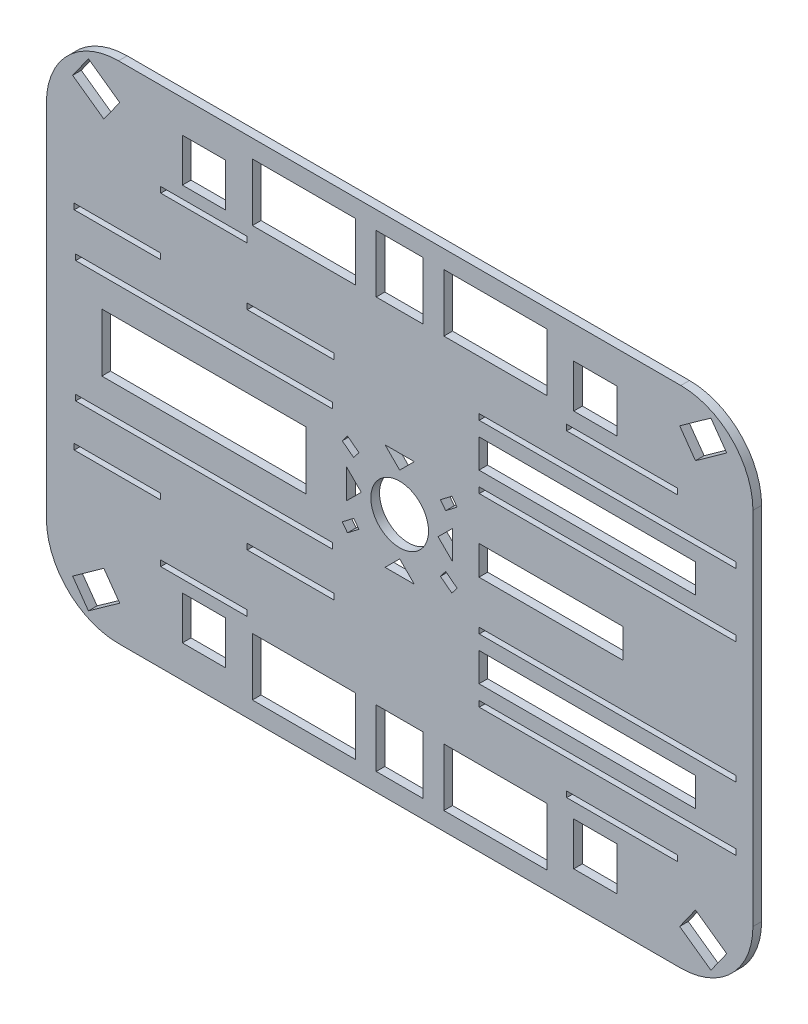
SolidWorks part; units mm, degrees
material "Hexcel AS4C (3000 Filaments)"
ref_plane "Front Plane" through (0, 0, 0) normal (0, 0, 1) x (1, 0, 0)
ref_plane "Top Plane" through (0, 0, 0) normal (0, 1, 0) x (1, 0, 0)
ref_plane "Right Plane" through (0, 0, 0) normal (1, 0, 0) x (0, 0, -1)
sketch "Sketch1" plane through (0, 0, 0) normal (0, 0, 1) x (1, 0, 0)
  line L1 (-122.5, 87.5) -> (122.5, 87.5)
  line L2 (-122.5, 87.5) -> (-122.5, -87.5)
  line L3 (-122.5, -87.5) -> (122.5, -87.5)
  line L4 (122.5, 87.5) -> (122.5, -87.5)
  line L5 (-122.5, 87.5) -> (122.5, -87.5) construction
  line L6 (-122.5, -87.5) -> (122.5, 87.5) construction
  point P0 (0, 0)
  dimension "D1" = 245
  dimension "D2" = 175
extrude "Boss-Extrude1" add sketch "Sketch1" along normal blind 3
sketch "Sketch2" plane through (0, 0, 3) normal (0, 0, 1) x (1, 0, 0)
  line L0 (0, 0) -> (-160.2379, 0) construction
  line L1 (0, 0) -> (163.7011, 0) construction
  line L2 (0, 94.1714) -> (0, -99.7658) construction
  line L3 (-52.8572, 37.0745) -> (-22.8572, 37.0745)
  line L4 (-103.2826, 10.0745) -> (-32.4317, 10.0745)
  line L5 (-103.2826, 10.0745) -> (-103.2826, -10.0745)
  line L6 (-103.2826, -10.0745) -> (-32.4317, -10.0745)
  line L7 (-32.4317, 10.0745) -> (-32.4317, -10.0745)
  line L8 (-103.2826, 10.0745) -> (-32.4317, -10.0745) construction
  line L9 (-103.2826, -10.0745) -> (-32.4317, 10.0745) construction
  line L10 (-112.3571, 22.0745) -> (-23.3572, 22.0745)
  line L11 (-112.3571, 22.0745) -> (-112.3571, 20.0745)
  line L12 (-112.3571, 20.0745) -> (-23.3572, 20.0745)
  line L13 (-23.3572, 22.0745) -> (-23.3572, 20.0745)
  line L14 (-112.3571, 22.0745) -> (-23.3572, 20.0745) construction
  line L15 (-112.3571, 20.0745) -> (-23.3572, 22.0745) construction
  line L16 (-52.8572, 37.0745) -> (-52.8572, 35.0745)
  line L17 (-52.8572, 35.0745) -> (-22.8572, 35.0745)
  line L18 (-22.8572, 37.0745) -> (-22.8572, 35.0745)
  line L19 (-52.8572, 37.0745) -> (-22.8572, 35.0745) construction
  line L20 (-52.8572, 35.0745) -> (-22.8572, 37.0745) construction
  line L21 (-112.8572, 37.0745) -> (-82.8572, 37.0745)
  line L22 (-112.8572, 37.0745) -> (-112.8572, 35.0745)
  line L23 (-112.8572, 35.0745) -> (-82.8572, 35.0745)
  line L24 (-82.8572, 37.0745) -> (-82.8572, 35.0745)
  line L25 (-112.8572, 37.0745) -> (-82.8572, 35.0745) construction
  line L26 (-112.8572, 35.0745) -> (-82.8572, 37.0745) construction
  line L27 (-67.8572, 0) -> (-67.8572, 112.1491) construction
  line L28 (-122.5, 87.5) -> (122.5, -87.5) construction
  line L29 (-52.8572, 57.0745) -> (-82.8572, 57.0745)
  line L30 (-52.8572, 57.0745) -> (-52.8572, 55.0745)
  line L31 (-52.8572, 55.0745) -> (-82.8572, 55.0745)
  line L32 (-82.8572, 57.0745) -> (-82.8572, 55.0745)
  line L33 (-52.8572, 57.0745) -> (-82.8572, 55.0745) construction
  line L34 (-52.8572, 55.0745) -> (-82.8572, 57.0745) construction
  line L35 (-8.142, 81.2412) -> (8.142, 81.2412)
  line L36 (-8.142, 81.2412) -> (-8.142, 61.2412)
  line L37 (-8.142, 61.2412) -> (8.142, 61.2412)
  line L38 (8.142, 81.2412) -> (8.142, 61.2412)
  line L39 (-8.142, 81.2412) -> (8.142, 61.2412) construction
  line L40 (-8.142, 61.2412) -> (8.142, 81.2412) construction
  line L41 (-51.0743, 81.2412) -> (-15.3203, 81.2412)
  line L42 (-51.0743, 81.2412) -> (-51.0743, 61.2412)
  line L43 (-51.0743, 61.2412) -> (-15.3203, 61.2412)
  line L44 (-15.3203, 81.2412) -> (-15.3203, 61.2412)
  line L45 (-51.0743, 81.2412) -> (-15.3203, 61.2412) construction
  line L46 (-51.0743, 61.2412) -> (-15.3203, 81.2412) construction
  line L47 (-75.3572, 76.24) -> (-60.3572, 76.24)
  line L48 (-75.3572, 76.24) -> (-75.3572, 61.24)
  line L49 (-75.3572, 61.24) -> (-60.3572, 61.24)
  line L50 (-60.3572, 76.24) -> (-60.3572, 61.24)
  line L51 (-75.3572, 76.24) -> (-60.3572, 61.24) construction
  line L52 (-75.3572, 61.24) -> (-60.3572, 76.24) construction
  line L53 (-113.4124, 75.1884) -> (-107.9269, 82.911)
  line L54 (-113.4124, 75.1884) -> (-102.5778, 67.4494)
  line L55 (-102.5778, 67.4494) -> (-97.0923, 75.1721)
  line L56 (-107.9269, 82.911) -> (-97.0923, 75.1721)
  line L57 (-113.4124, 75.1884) -> (-97.0923, 75.1721) construction
  line L58 (-102.5778, 67.4494) -> (-107.9269, 82.911) construction
  line L59 (-105.2523, 75.1802) -> (-110.6696, 79.0497)
  line L60 (-102.5778, -67.4494) -> (-107.9269, -82.911) construction
  line L61 (-113.4124, -75.1884) -> (-97.0923, -75.1721) construction
  line L62 (-75.3572, -61.24) -> (-60.3572, -76.24) construction
  line L63 (-75.3572, -76.24) -> (-60.3572, -61.24) construction
  line L64 (-51.0743, -61.2412) -> (-15.3203, -81.2412) construction
  line L65 (-51.0743, -81.2412) -> (-15.3203, -61.2412) construction
  line L66 (-52.8572, -55.0745) -> (-82.8572, -57.0745) construction
  line L67 (-52.8572, -57.0745) -> (-82.8572, -55.0745) construction
  line L68 (-67.8572, 0) -> (-67.8572, -112.1491) construction
  line L69 (-112.8572, -35.0745) -> (-82.8572, -37.0745) construction
  line L70 (-112.8572, -37.0745) -> (-82.8572, -35.0745) construction
  line L71 (-52.8572, -35.0745) -> (-22.8572, -37.0745) construction
  line L72 (-52.8572, -37.0745) -> (-22.8572, -35.0745) construction
  line L73 (-112.3571, -20.0745) -> (-23.3572, -22.0745) construction
  line L74 (-112.3571, -22.0745) -> (-23.3572, -20.0745) construction
  line L75 (-105.2523, -75.1802) -> (-110.6696, -79.0497)
  line L76 (-107.9269, -82.911) -> (-97.0923, -75.1721)
  line L77 (-102.5778, -67.4494) -> (-97.0923, -75.1721)
  line L78 (-113.4124, -75.1884) -> (-102.5778, -67.4494)
  line L79 (-113.4124, -75.1884) -> (-107.9269, -82.911)
  line L80 (-60.3572, -76.24) -> (-60.3572, -61.24)
  line L81 (-75.3572, -61.24) -> (-60.3572, -61.24)
  line L82 (-75.3572, -76.24) -> (-75.3572, -61.24)
  line L83 (-75.3572, -76.24) -> (-60.3572, -76.24)
  line L84 (-15.3203, -81.2412) -> (-15.3203, -61.2412)
  line L85 (-51.0743, -61.2412) -> (-15.3203, -61.2412)
  line L86 (-51.0743, -81.2412) -> (-51.0743, -61.2412)
  line L87 (-51.0743, -81.2412) -> (-15.3203, -81.2412)
  line L88 (-8.142, -81.2412) -> (-8.142, -61.2412)
  line L89 (-82.8572, -57.0745) -> (-82.8572, -55.0745)
  line L90 (-52.8572, -55.0745) -> (-82.8572, -55.0745)
  line L91 (-52.8572, -57.0745) -> (-52.8572, -55.0745)
  line L92 (-52.8572, -57.0745) -> (-82.8572, -57.0745)
  line L93 (-82.8572, -37.0745) -> (-82.8572, -35.0745)
  line L94 (-112.8572, -35.0745) -> (-82.8572, -35.0745)
  line L95 (-112.8572, -37.0745) -> (-112.8572, -35.0745)
  line L96 (-112.8572, -37.0745) -> (-82.8572, -37.0745)
  line L97 (-22.8572, -37.0745) -> (-22.8572, -35.0745)
  line L98 (-52.8572, -35.0745) -> (-22.8572, -35.0745)
  line L99 (-52.8572, -37.0745) -> (-52.8572, -35.0745)
  line L100 (-23.3572, -22.0745) -> (-23.3572, -20.0745)
  line L101 (-112.3571, -20.0745) -> (-23.3572, -20.0745)
  line L102 (-112.3571, -22.0745) -> (-112.3571, -20.0745)
  line L103 (-112.3571, -22.0745) -> (-23.3572, -22.0745)
  line L104 (27.5911, -42.0745) -> (116.5911, -42.0745)
  line L105 (-52.8572, -37.0745) -> (-22.8572, -37.0745)
  line L106 (27.5029, 5.0745) -> (77.5029, 5.0745)
  line L107 (27.5029, 5.0745) -> (27.5029, -5.0745)
  line L108 (27.5029, -5.0745) -> (77.5029, -5.0745)
  line L109 (77.5029, 5.0745) -> (77.5029, -5.0745)
  line L110 (27.5029, 5.0745) -> (77.5029, -5.0745) construction
  line L111 (27.5029, -5.0745) -> (77.5029, 5.0745) construction
  line L112 (27.5911, -20.0745) -> (116.5911, -20.0745)
  line L113 (27.5911, -20.0745) -> (27.5911, -22.0745)
  line L114 (27.5911, -22.0745) -> (116.5911, -22.0745)
  line L115 (116.5911, -20.0745) -> (116.5911, -22.0745)
  line L116 (27.5911, -20.0745) -> (116.5911, -22.0745) construction
  line L117 (27.5911, -22.0745) -> (116.5911, -20.0745) construction
  line L118 (27.5029, -37.0745) -> (102.5029, -37.0745)
  line L119 (27.5029, -37.0745) -> (27.5029, -27.0745)
  line L120 (27.5029, -27.0745) -> (102.5029, -27.0745)
  line L121 (102.5029, -37.0745) -> (102.5029, -27.0745)
  line L122 (27.5029, -37.0745) -> (102.5029, -27.0745) construction
  line L123 (27.5029, -27.0745) -> (102.5029, -37.0745) construction
  line L124 (27.5911, -44.0745) -> (116.5911, -44.0745)
  line L125 (116.5911, -42.0745) -> (116.5911, -44.0745)
  line L126 (27.5911, -42.0745) -> (116.5911, -44.0745) construction
  line L127 (27.5911, -44.0745) -> (116.5911, -42.0745) construction
  line L128 (27.5911, -44.0745) -> (27.5911, -42.0745)
  line L129 (107.9269, -82.911) -> (97.0923, -75.1721)
  line L130 (113.4124, -75.1884) -> (107.9269, -82.911)
  line L131 (113.4124, -75.1884) -> (102.5778, -67.4494)
  line L132 (102.5778, -67.4494) -> (97.0923, -75.1721)
  line L133 (-15, -35.0745) -> (15, -37.0745) construction
  line L134 (-15, -37.0745) -> (15, -35.0745) construction
  line L135 (15, -37.0745) -> (15, -35.0745)
  line L136 (-15, -35.0745) -> (15, -35.0745)
  line L137 (-15, -37.0745) -> (-15, -35.0745)
  line L138 (-15, -37.0745) -> (15, -37.0745)
  line L139 (-122.5, 87.5) -> (122.5, 87.5) construction
  line L140 (-8.142, -81.2412) -> (8.142, -81.2412)
  line L141 (8.142, -81.2412) -> (8.142, -61.2412)
  line L142 (-8.142, -61.2412) -> (8.142, -61.2412)
  line L143 (113.4124, -75.1884) -> (107.9269, -82.911)
  line L144 (113.4124, -75.1884) -> (102.5778, -67.4494)
  line L145 (102.5778, -67.4494) -> (97.0923, -75.1721)
  line L146 (107.9269, -82.911) -> (97.0923, -75.1721)
  line L147 (75.3572, -76.24) -> (60.3572, -76.24)
  line L148 (75.3572, -76.24) -> (75.3572, -61.24)
  line L149 (75.3572, -61.24) -> (60.3572, -61.24)
  line L150 (60.3572, -76.24) -> (60.3572, -61.24)
  line L151 (51.0743, -81.2412) -> (15.3203, -81.2412)
  line L152 (51.0743, -81.2412) -> (51.0743, -61.2412)
  line L153 (51.0743, -61.2412) -> (15.3203, -61.2412)
  line L154 (15.3203, -81.2412) -> (15.3203, -61.2412)
  line L155 (102.5778, 67.4494) -> (97.0923, 75.1721)
  line L156 (107.9269, 82.911) -> (97.0923, 75.1721)
  line L157 (113.4124, 75.1884) -> (107.9269, 82.911)
  line L158 (113.4124, 75.1884) -> (102.5778, 67.4494)
  line L159 (75.3572, 61.24) -> (60.3572, 61.24)
  line L160 (60.3572, 76.24) -> (60.3572, 61.24)
  line L161 (75.3572, 76.24) -> (60.3572, 76.24)
  line L162 (75.3572, 76.24) -> (75.3572, 61.24)
  line L163 (51.0743, 61.2412) -> (15.3203, 61.2412)
  line L164 (15.3203, 81.2412) -> (15.3203, 61.2412)
  line L165 (51.0743, 81.2412) -> (15.3203, 81.2412)
  line L166 (51.0743, 81.2412) -> (51.0743, 61.2412)
  line L167 (27.5911, 44.0745) -> (116.5911, 44.0745)
  line L168 (116.5911, 42.0745) -> (116.5911, 44.0745)
  line L169 (27.5911, 42.0745) -> (116.5911, 42.0745)
  line L170 (27.5911, 44.0745) -> (27.5911, 42.0745)
  line L171 (27.5911, 22.0745) -> (116.5911, 22.0745)
  line L172 (116.5911, 20.0745) -> (116.5911, 22.0745)
  line L173 (27.5911, 20.0745) -> (116.5911, 20.0745)
  line L174 (27.5911, 20.0745) -> (27.5911, 22.0745)
  line L175 (27.5029, 27.0745) -> (102.5029, 27.0745)
  line L176 (102.5029, 37.0745) -> (102.5029, 27.0745)
  line L177 (27.5029, 37.0745) -> (102.5029, 37.0745)
  line L178 (27.5029, 37.0745) -> (27.5029, 27.0745)
  line L179 (-122.5, -87.5) -> (122.5, 87.5) construction
  line L180 (57.9068, 56.0745) -> (96.3019, 56.0745)
  line L181 (57.9068, 56.0745) -> (57.9068, 54.0745)
  line L182 (57.9068, 54.0745) -> (96.3019, 54.0745)
  line L183 (96.3019, 56.0745) -> (96.3019, 54.0745)
  line L184 (57.9068, 56.0745) -> (96.3019, 54.0745) construction
  line L185 (57.9068, 54.0745) -> (96.3019, 56.0745) construction
  line L186 (57.9068, -54.0745) -> (96.3019, -54.0745)
  line L187 (96.3019, -56.0745) -> (96.3019, -54.0745)
  line L188 (57.9068, -56.0745) -> (96.3019, -56.0745)
  line L189 (57.9068, -56.0745) -> (57.9068, -54.0745)
  line L190 (-18.4042, 5.0745) -> (-18.4042, -5.0745)
  line L191 (-18.4042, -5.0745) -> (-13.3297, 0)
  line L192 (-13.3297, 0) -> (-18.4042, 5.0745)
  line L193 (0, 13.3297) -> (5.0745, 18.4042)
  line L194 (5.0745, 18.4042) -> (-5.0745, 18.4042)
  line L195 (-5.0745, 18.4042) -> (0, 13.3297)
  line L196 (13.3297, 0) -> (18.4042, -5.0745)
  line L197 (18.4042, -5.0745) -> (18.4042, 5.0745)
  line L198 (18.4042, 5.0745) -> (13.3297, 0)
  line L199 (0, -13.3297) -> (-5.0745, -18.4042)
  line L200 (-5.0745, -18.4042) -> (5.0745, -18.4042)
  line L201 (5.0745, -18.4042) -> (0, -13.3297)
  line L202 (15.955, -9.1246) -> (19.92, -12.1708)
  line L203 (19.92, -12.1708) -> (18.0922, -14.5497)
  line L204 (18.0922, -14.5497) -> (14.1273, -11.5035)
  line L205 (14.1273, -11.5035) -> (15.955, -9.1246)
  line L206 (18.0922, 14.5497) -> (14.1273, 11.5035)
  line L207 (19.92, 12.1708) -> (18.0922, 14.5497)
  line L208 (15.955, 9.1246) -> (19.92, 12.1708)
  line L209 (14.1273, 11.5035) -> (15.955, 9.1246)
  line L210 (-19.92, 12.1708) -> (-18.0922, 14.5497)
  line L211 (-15.955, 9.1246) -> (-19.92, 12.1708)
  line L212 (-14.1273, 11.5035) -> (-15.955, 9.1246)
  line L213 (-18.0922, 14.5497) -> (-14.1273, 11.5035)
  line L214 (-18.0922, -14.5497) -> (-14.1273, -11.5035)
  line L215 (-19.92, -12.1708) -> (-18.0922, -14.5497)
  line L216 (-15.955, -9.1246) -> (-19.92, -12.1708)
  line L217 (-14.1273, -11.5035) -> (-15.955, -9.1246)
  circle A0 centre (0, 0) radius 10
  point P7 (-67.8572, 0)
  point P12 (-67.8572, 21.0745)
  point P17 (-37.8572, 36.0745)
  point P22 (-97.8572, 36.0745)
  point P27 (-67.8572, 56.0745)
  point P32 (0, 71.2412)
  point P39 (-33.1973, 71.2412)
  point P44 (-105.2523, 75.1802)
  point P47 (-67.8572, 68.74)
  point P91 (-67.8572, -68.74)
  point P92 (-105.2523, -75.1802)
  point P93 (-33.1973, -71.2412)
  point P94 (0, -71.2412)
  point P95 (-67.8572, -56.0745)
  point P96 (-97.8572, -36.0745)
  point P97 (-37.8572, -36.0745)
  point P98 (-67.8572, -21.0745)
  point P99 (52.5029, 0)
  point P104 (72.0911, -21.0745)
  point P110 (65.0029, -32.0745)
  point P126 (0, -54.7099)
  point P127 (77.1043, 55.0745)
  point P177 (0, 20.0745)
  point P178 (-18.4042, 0)
  dimension "D1" = 30
  dimension "D2" = 2
  dimension "D3" = 30
  dimension "D4" = 30
  dimension "D5" = 2
  dimension "D6" = 30
  dimension "D7" = 2
  dimension "D8" = 2
  dimension "D9" = 30
  dimension "D10" = 10
  dimension "D11" = 45
  dimension "D12" = 50
  dimension "D13" = 88.9998
  dimension "D14" = 2
  dimension "D15" = 89
  dimension "D16" = 15
  dimension "D17" = 15
  dimension "D18" = 89
  dimension "D19" = 15
  dimension "D20" = 0
  dimension "D21" = 30
  dimension "D22" = 2
  dimension "D23" = 20
  dimension "D24" = 20
  dimension "D25" = 15
  dimension "D26" = 15
  dimension "D27" = 26.2588
  dimension "D28" = 26.26
  dimension "D29" = 10
  dimension "D30" = 2
  dimension "D31" = 15
  dimension "D32" = 2
  dimension "D34" = 3
  dimension "D35" = 5
  dimension "D33" = 4
extrude "Cut-Extrude1" cut sketch "Sketch2" against normal through all contours L50 L47 L48 L49 | L44 L41 L42 L43 | L38 L35 L36 L37 | L56 L53 L54 L55 | L29 L32 L31 L30 | L24 L21 L22 L23 | L18 L3 L16 L17 | L13 L10 L11 L12 | L7 L4 L5 L6 | A0 | L102 L103 L100 L101 | L99 L105 L97 L98 | L95 L96 L93 L94 | L92 L91 L90 L89 | L78 L79 L76 L77 | L82 L83 L80 L81 | L86 L87 L84 L85 | L56 L55 L54 L53 region at (-37.8572, 36.0745, 3) region at (-67.8572, 0, 3) region at (-67.8572, 21.0745, 3) region at (-97.8572, 36.0745, 3) region at (-67.8572, 56.0745, 3) region at (0, 71.2412, 3) region at (-33.1973, 71.2412, 3) region at (-67.8572, 68.74, 3) region at (-111.8577, 76.9889, 3) region at (-109.115, -80.8502, 3) region at (-67.8572, -68.74, 3) region at (-33.1973, -71.2412, 3) region at (-67.8572, -56.0745, 3) region at (-97.8572, -36.0745, 3) region at (-37.8572, -36.0745, 3) region at (-67.8572, -21.0745, 3) region at (0, 0, 3)
fillet "Fillet1" radius 25 4 edges at (-122.5, -87.5, 1.5) (122.5, -87.5, 1.5) (122.5, 87.5, 1.5) (-122.5, 87.5, 1.5)
extrude "Cut-Extrude2" cut sketch "Sketch2<4>" against normal blind 10 contours L166 L165 L164 L163 | L162 L161 L160 L159 | L158 L157 L156 L155 | L183 L180 L181 L182 | L177 L178 L175 L176 | L174 L173 L172 L171 | L109 L106 L107 L108 | L115 L112 L113 L114 | L118 L121 L120 L119 | L128 L124 L125 L104 | L154 L151 L152 L153 | L150 L147 L148 L149 | L131 L132 L129 L130 | L167 L168 L169 L170 | L186 L187 L188 L189 region at (72.0911, -43.0745, 3) region at (52.5029, 0, 3) region at (72.0911, -21.0745, 3) region at (65.0029, -32.0745, 3) region at (105.2523, -75.1802, 3) region at (67.8572, -68.74, 3) region at (33.1973, -71.2412, 3) region at (105.2523, 75.1802, 3) region at (67.8572, 68.74, 3) region at (33.1973, 71.2412, 3) region at (72.0911, 21.0745, 3) region at (65.0029, 32.0745, 3) region at (77.1043, 55.0745, 3)
sketch "Sketch2<4>" plane through (0, 0, 3) normal (0, 0, 1) x (1, 0, 0) same geometry as "Sketch2"
extrude "Cut-Extrude3" cut sketch "Sketch2<5>" against normal blind 10 contours L142 L88 L140 L141 region at (0, -71.2412, 3)
sketch "Sketch2<5>" plane through (0, 0, 3) normal (0, 0, 1) x (1, 0, 0) same geometry as "Sketch2"
extrude "Cut-Extrude4" cut sketch "Sketch2<6>" against normal blind 10 contours L194 L195 L193 | L191 L192 L190 | L200 L201 L199 | L197 L198 L196 region at (-16.7127, 0, 3) region at (0, 16.7127, 3) region at (16.7127, 0, 3) region at (0, -16.7127, 3)
sketch "Sketch2<6>" plane through (0, 0, 3) normal (0, 0, 1) x (1, 0, 0) same geometry as "Sketch2"
extrude "Cut-Extrude5" cut sketch "Sketch2<7>" against normal blind 10 contours L205 L204 L203 L202 | L206 L209 L208 L207 | L213 L210 L211 L212 | L214 L217 L216 L215 region at (17.0236, -11.8371, 3) region at (17.0236, 11.8371, 3) region at (-17.0236, 11.8371, 3) region at (-17.0236, -11.8371, 3)
sketch "Sketch2<7>" plane through (0, 0, 3) normal (0, 0, 1) x (1, 0, 0) same geometry as "Sketch2"
